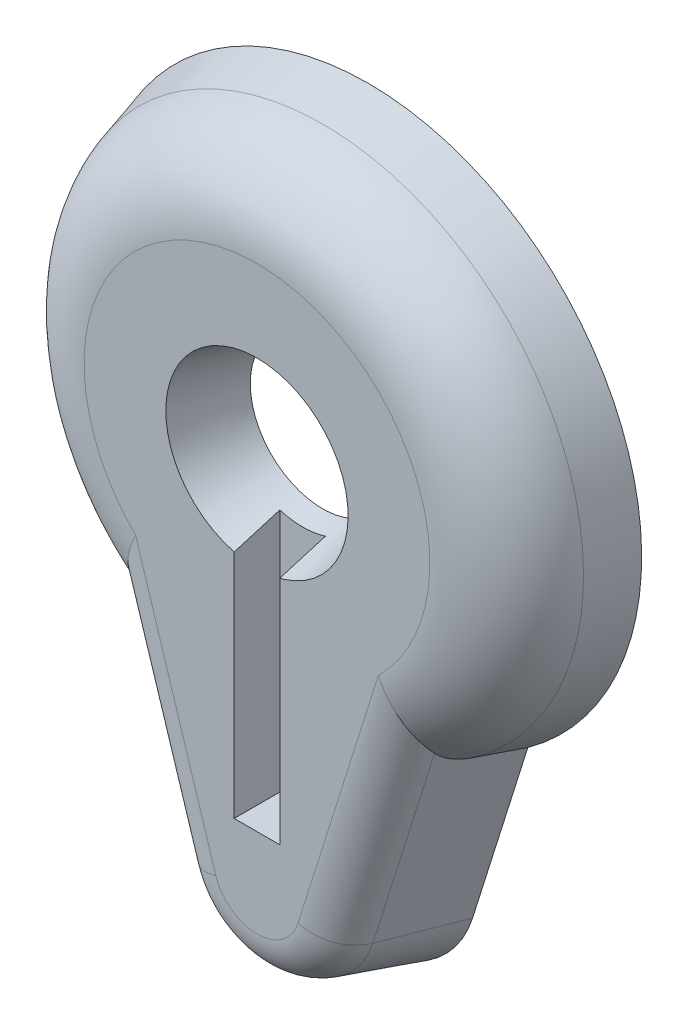
SolidWorks part; units mm, degrees
ref_plane "Front Plane" through (0, 0, 0) normal (0, 0, 1) x (1, 0, 0)
ref_plane "Top Plane" through (0, 0, 0) normal (0, 1, 0) x (1, 0, 0)
ref_plane "Right Plane" through (0, 0, 0) normal (1, 0, 0) x (0, 0, -1)
sketch "Sketch1" plane through (0, 0, 0) normal (0, 0, 1) x (1, 0, 0)
  line L0 (0, 0) -> (0, 62.9175) construction
  line L1 (-14.5346, -4.5828) -> (-22.2438, 19.8674)
  line L2 (14.5346, -4.5828) -> (22.2438, 19.8674)
  arc A0 (-14.5346, -4.5828) -> (14.5346, -4.5828) centre (0, 0) ccw
  arc A1 (-22.2438, 19.8674) -> (22.2438, 19.8674) centre (0, 50.8) cw
  point P9 (0, 0)
  point P10 (0, -7.5758)
  point P11 (0, 0)
  point P12 (0, 0)
  point P13 (0, 1.8218)
  dimension "D1" = 15.24
  dimension "D2" = 38.1
  dimension "D3" = 50.8
  dimension "D4" = 35
extrude "Boss-Extrude1" add sketch "Sketch1" along normal blind 15.494 draft 16
fillet "Fillet1" radius 6.35 3 edges at (14.3818, 9.7071, 15.494) (0, -10.7972, 15.494) (-14.3818, 9.7071, 15.494)
fillet "Fillet2" radius 12.7 1 edges at (0, 84.4572, 15.494)
sketch "Sketch3" plane through (0, 0, 0) normal (0, 0, -1) x (-1, 0, 0)
  line L4 (12.1122, -3.819) -> (20.0801, 21.4521)
  line L5 (-20.0801, 21.4521) -> (-12.1122, -3.819)
  line L6 (12.1122, -3.819) -> (20.0801, 21.4521)
  line L7 (-20.0801, 21.4521) -> (-12.1122, -3.819)
  arc A4 (-12.1122, -3.819) -> (12.1122, -3.819) centre (0, 0) ccw
  arc A5 (20.0801, 21.4521) -> (-20.0801, 21.4521) centre (0, 50.8) ccw
  arc A6 (-12.1122, -3.819) -> (12.1122, -3.819) centre (0, 0) ccw
  arc A7 (20.0801, 21.4521) -> (-20.0801, 21.4521) centre (0, 50.8) ccw
  dimension "D1" = 2.54
extrude "Cut-Extrude3" cut sketch "Sketch3" against normal blind 6.35 draft 16
sketch "Sketch4" plane through (0, 0, 15.494) normal (0, 0, 1) x (1, 0, 0)
  circle A0 centre (0, 50.8) radius 12.7
  dimension "D1" = 25.4
extrude "Cut-Extrude6" cut sketch "Sketch4" against normal through all draft 16
sketch "Sketch7" plane through (0, 0, 15.494) normal (0, 0, 1) x (1, 0, 0)
  line L0 (0, 0) -> (0, 51.2343) construction
  line L1 (0, 6.35) -> (0, 0) construction
  line L2 (-3.175, 57.15) -> (3.175, 57.15)
  line L3 (-3.175, 57.15) -> (-3.175, 6.35)
  line L4 (-3.175, 6.35) -> (3.175, 6.35)
  line L5 (3.175, 57.15) -> (3.175, 6.35)
  point P9 (0, -1.3631)
  dimension "D1" = 50.8
  dimension "D2" = 6.35
  dimension "D3" = 6.35
extrude "Cut-Extrude10" cut sketch "Sketch7" against normal blind 6.35
